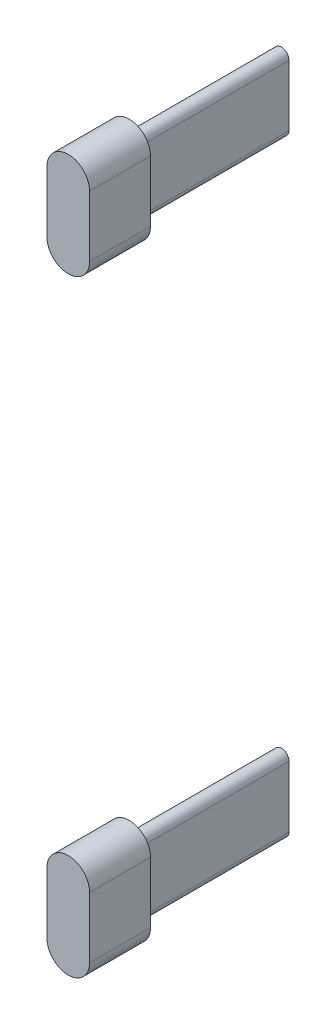
SolidWorks part; units mm, degrees
ref_plane "前视基准面" through (0, 0, 0) normal (0, 0, 1) x (1, 0, 0)
ref_plane "上视基准面" through (0, 0, 0) normal (0, 1, 0) x (1, 0, 0)
ref_plane "右视基准面" through (0, 0, 0) normal (1, 0, 0) x (0, 0, -1)
other "Configuration Table"
sketch "草图1" plane through (0, 0, 0) normal (0, 0, 1) x (1, 0, 0)
  line L0 (-4.3532, -34.1185) -> (-4.3532, -26.1185)
  line L1 (-6.3532, -26.1185) -> (-6.3532, -34.1185)
  line L2 (-3.8532, -113.8815) -> (-3.8532, -105.8815)
  line L3 (-6.8532, -105.8815) -> (-6.8532, -113.8815)
  line L4 (-3.8532, -113.8815) -> (-3.8532, -105.8815) construction
  line L5 (-6.8532, -105.8815) -> (-6.8532, -113.8815) construction
  line L6 (-3.8532, -34.1185) -> (-3.8532, -26.1185)
  line L7 (-6.8532, -26.1185) -> (-6.8532, -34.1185)
  line L8 (-3.8532, -34.1185) -> (-3.8532, -26.1185) construction
  line L9 (-6.8532, -26.1185) -> (-6.8532, -34.1185) construction
  line L10 (-4.3532, -113.8815) -> (-4.3532, -105.8815)
  line L11 (-6.3532, -105.8815) -> (-6.3532, -113.8815)
  arc A0 (-4.3532, -26.1185) -> (-6.3532, -26.1185) centre (-5.3532, -26.1185) ccw
  arc A1 (-6.3532, -34.1185) -> (-4.3532, -34.1185) centre (-5.3532, -34.1185) ccw
  arc A2 (-3.8532, -105.8815) -> (-6.8532, -105.8815) centre (-5.3532, -105.8815) ccw
  arc A3 (-6.8532, -113.8815) -> (-3.8532, -113.8815) centre (-5.3532, -113.8815) ccw
  arc A4 (-3.8532, -105.8815) -> (-6.8532, -105.8815) centre (-5.3532, -105.8815) ccw construction
  arc A5 (-6.8532, -113.8815) -> (-3.8532, -113.8815) centre (-5.3532, -113.8815) ccw construction
  arc A6 (-6.8532, -34.1185) -> (-3.8532, -34.1185) centre (-5.3532, -34.1185) ccw
  arc A7 (-3.8532, -26.1185) -> (-6.8532, -26.1185) centre (-5.3532, -26.1185) ccw
  arc A8 (-6.8532, -34.1185) -> (-3.8532, -34.1185) centre (-5.3532, -34.1185) ccw construction
  arc A9 (-3.8532, -26.1185) -> (-6.8532, -26.1185) centre (-5.3532, -26.1185) ccw construction
  arc A10 (-4.3532, -105.8815) -> (-6.3532, -105.8815) centre (-5.3532, -105.8815) ccw
  arc A11 (-6.3532, -113.8815) -> (-4.3532, -113.8815) centre (-5.3532, -113.8815) ccw
  dimension "D4" = 8
  dimension "D3" = 2
  dimension "D1" = 0
  dimension "D2" = 0
extrude "凸台-拉伸1" add sketch "草图1" against normal blind 20
sketch "草图2" plane through (0, 0, 0) normal (0, 0, 1) x (1, 0, 0)
  line L0 (-4.3532, -113.8815) -> (-4.3532, -105.8815) construction
  line L1 (-6.3532, -105.8815) -> (-6.3532, -113.8815) construction
  line L2 (-4.3532, -34.1185) -> (-4.3532, -26.1185) construction
  line L3 (-6.3532, -26.1185) -> (-6.3532, -34.1185) construction
  line L4 (-4.3532, -113.8815) -> (-4.3532, -105.8815) construction
  line L5 (-6.3532, -105.8815) -> (-6.3532, -113.8815) construction
  line L6 (-4.3532, -34.1185) -> (-4.3532, -26.1185) construction
  line L7 (-6.3532, -26.1185) -> (-6.3532, -34.1185) construction
  line L8 (-8.1532, -105.8815) -> (-8.1532, -113.8815)
  line L9 (-2.5532, -113.8815) -> (-2.5532, -105.8815)
  line L10 (-8.1532, -26.1185) -> (-8.1532, -34.1185)
  line L11 (-2.5532, -34.1185) -> (-2.5532, -26.1185)
  arc A0 (-6.3532, -113.8815) -> (-4.3532, -113.8815) centre (-5.3532, -113.8815) ccw construction
  arc A1 (-4.3532, -105.8815) -> (-6.3532, -105.8815) centre (-5.3532, -105.8815) ccw construction
  arc A2 (-6.3532, -34.1185) -> (-4.3532, -34.1185) centre (-5.3532, -34.1185) ccw construction
  arc A3 (-4.3532, -26.1185) -> (-6.3532, -26.1185) centre (-5.3532, -26.1185) ccw construction
  arc A4 (-6.3532, -113.8815) -> (-4.3532, -113.8815) centre (-5.3532, -113.8815) ccw construction
  arc A5 (-4.3532, -105.8815) -> (-6.3532, -105.8815) centre (-5.3532, -105.8815) ccw construction
  arc A6 (-6.3532, -34.1185) -> (-4.3532, -34.1185) centre (-5.3532, -34.1185) ccw construction
  arc A7 (-4.3532, -26.1185) -> (-6.3532, -26.1185) centre (-5.3532, -26.1185) ccw construction
  arc A8 (-8.1532, -113.8815) -> (-2.5532, -113.8815) centre (-5.3532, -113.8815) ccw
  arc A9 (-2.5532, -105.8815) -> (-8.1532, -105.8815) centre (-5.3532, -105.8815) ccw
  arc A10 (-8.1532, -34.1185) -> (-2.5532, -34.1185) centre (-5.3532, -34.1185) ccw
  arc A11 (-2.5532, -26.1185) -> (-8.1532, -26.1185) centre (-5.3532, -26.1185) ccw
extrude "凸台-拉伸2" add sketch "草图2" along normal blind 8
